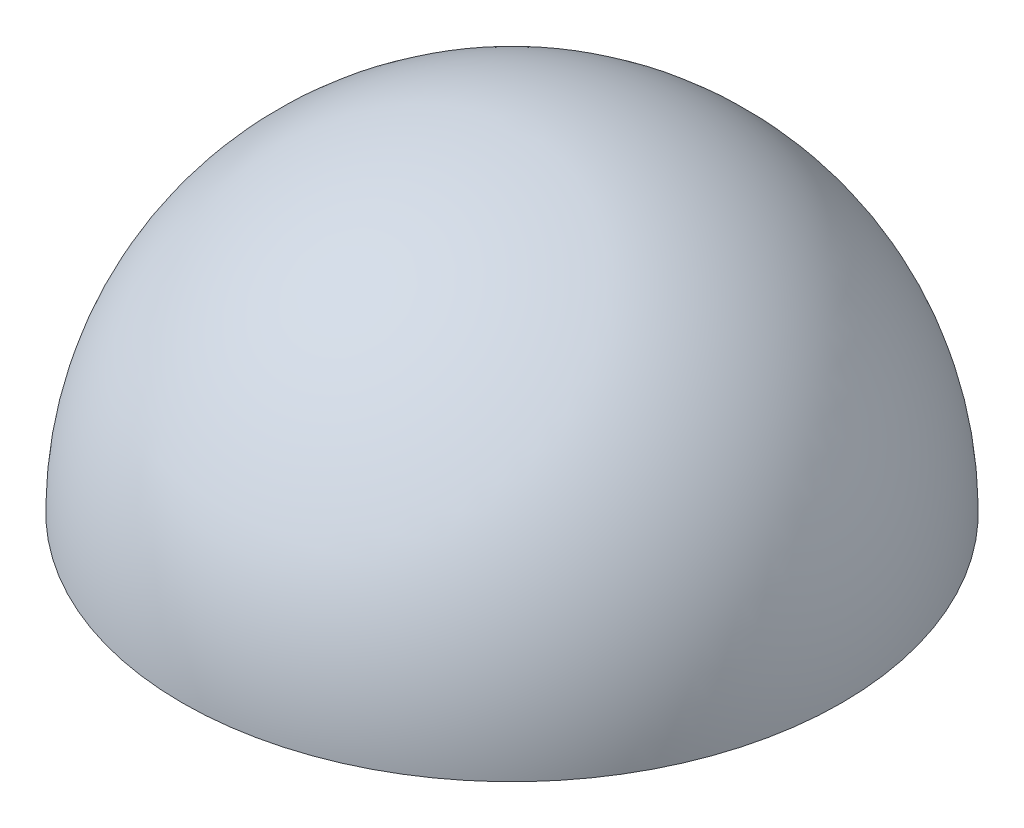
SolidWorks part; units mm, degrees
ref_plane "Front Plane" through (0, 0, 0) normal (0, 0, 1) x (1, 0, 0)
ref_plane "Top Plane" through (0, 0, 0) normal (0, 1, 0) x (1, 0, 0)
ref_plane "Right Plane" through (0, 0, 0) normal (1, 0, 0) x (0, 0, -1)
sketch "Sketch8" plane through (0, 0, 0) normal (0, 0, 1) x (1, 0, 0)
  line L0 (0, -5) -> (0, 0) construction
  line L2 (0, 5) -> (0, -5)
  arc A1 (0, -5) -> (0, 5) centre (0, 0) ccw
  dimension "D1" = 5
revolve "Revolve5" add sketch "Sketch8" angle 360 about L0 reverse direction yes
sketch "Sketch9" plane through (0, 0, 0) normal (0, 1, 0) x (1, 0, 0)
  circle A0 centre (0, 0) radius 5
  dimension "D1" = 10
extrude "Cut-Extrude1" cut sketch "Sketch9" against normal blind 5
sketch "Sketch10" plane through (0, 0, 0) normal (0, -1, 0) x (1, 0, 0)
  point P0 (0, 0)
